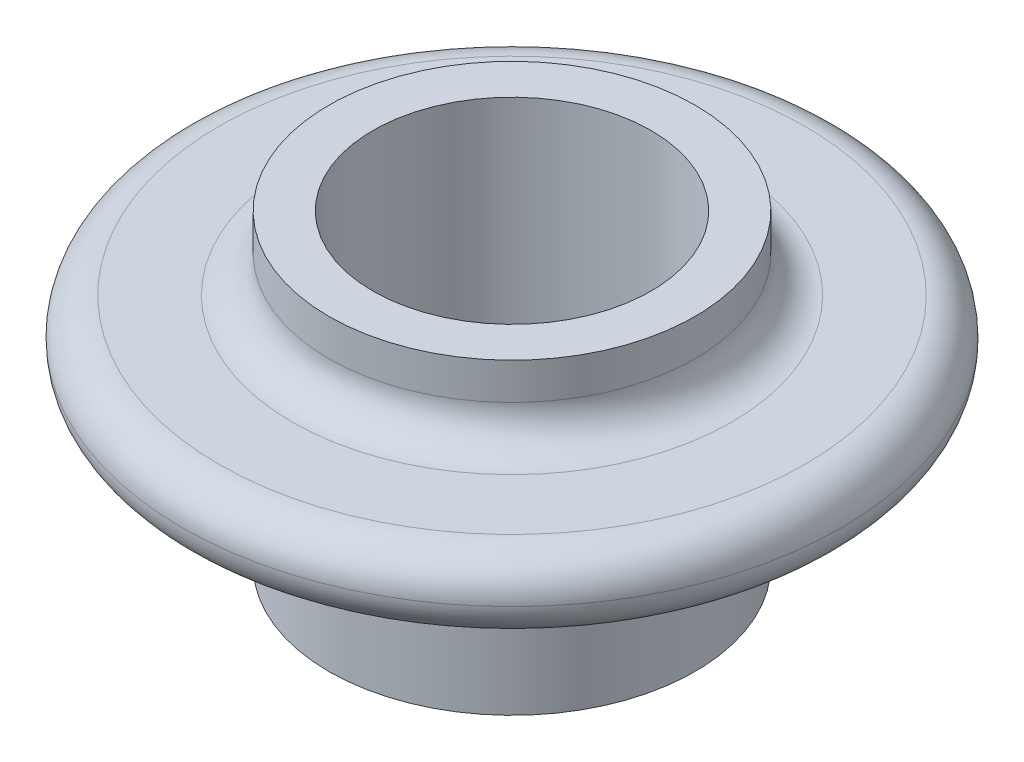
SolidWorks part; units mm, degrees
ref_plane "Front Plane" through (0, 0, 0) normal (0, 0, 1) x (1, 0, 0)
ref_plane "Top Plane" through (0, 0, 0) normal (0, 1, 0) x (1, 0, 0)
ref_plane "Right Plane" through (0, 0, 0) normal (1, 0, 0) x (0, 0, -1)
sketch "Sketch1" plane through (0, 0, 0) normal (0, 0, 1) x (1, 0, 0)
  line L0 (19, 0) -> (19, 42)
  line L1 (19, 42) -> (25, 42)
  line L2 (25, 42) -> (25, 32)
  line L3 (25, 32) -> (45, 32)
  line L4 (45, 32) -> (45, 22)
  line L5 (45, 22) -> (25, 22)
  line L6 (25, 22) -> (25, 0)
  line L7 (25, 0) -> (19, 0)
  line L8 (0, 0) -> (0, 27.9255) construction
  dimension "D1" = 19
  dimension "D2" = 25
  dimension "D3" = 45
  dimension "D4" = 42
  dimension "D5" = 10
  dimension "D6" = 10
revolve "Revolve1" add sketch "Sketch1" angle 360 about L8
fillet "Fillet1" radius 5 3 edges at (0, 32, -25) (0, 22, -45) (0, 32, -45)
